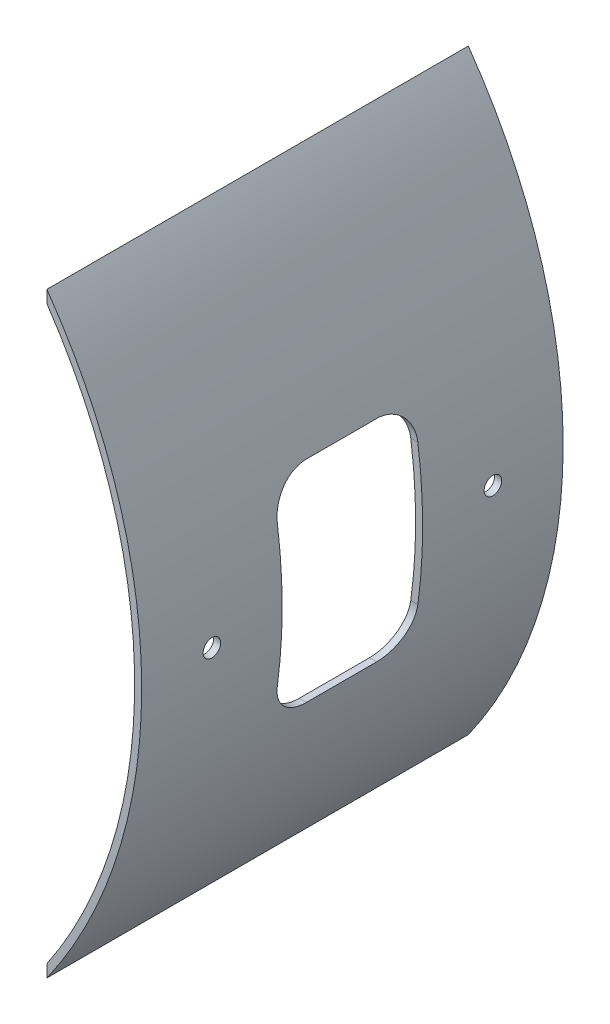
SolidWorks part; units mm, degrees
ref_plane "Face" through (0, 0, 0) normal (0, 0, 1) x (1, 0, 0)
ref_plane "Dessus" through (0, 0, 0) normal (0, 1, 0) x (1, 0, 0)
ref_plane "Droite" through (0, 0, 0) normal (1, 0, 0) x (0, 0, -1)
sketch "Esquisse1" plane through (0, 0, 0) normal (0, 0, 1) x (1, 0, 0)
  line L0 (120, 84.9058) -> (120, 81.3941)
  line L1 (120, -81.3941) -> (120, -84.9058)
  arc A0 (120, -84.9058) -> (120, 84.9058) centre (0, 0) ccw
  arc A1 (120, -81.3941) -> (120, 81.3941) centre (0, 0) ccw
  dimension "D1" = 294
  dimension "D2" = 2
  dimension "D3" = 120
extrude "Boss.-Extru.1" add sketch "Esquisse1" along normal blind 120
hole_wizard "Diamètre du perçage Ø5.0 (5)1" positions "Esquisse3D1" profile "Esquisse2" hole size "Ø5.0" standard "Din"
sketch3d "Esquisse3D1"
  point P0 (147, 0, 20)
  point P12 (147, 0, 100)
sketch "Esquisse2" plane through (147, 0, 20) normal (0, 1, 0) x (0, 0, -1)
  line L0 (0, 0) -> (0, 61.5022)
  line L1 (0, 61.5022) -> (2.5, 60)
  line L2 (2.5, 60) -> (2.5, 0)
  line L5 (2.5, 0) -> (0, 0)
  line L10 (0, 61.5022) -> (-2.5, 60) construction
  line L11 (0, -6.35) -> (0, 107.95) construction
  dimension "Diamètre du perçage" = 5
  dimension "Profondeur du perçage" = 60
  dimension "Angle de pointe" = 118
ref_axis "Axe1" through (0, 0, 120) along (0, 0, -1)
sketch "Esquisse3" plane through (0, 0, 0) normal (1, 0, 0) x (0, 0, -1)
  line L0 (0, -84.9058) -> (0, 84.9058) construction
  line L1 (-70, 30) -> (-50, 30)
  line L2 (-80, 20) -> (-80, -20)
  line L3 (-70, -30) -> (-50, -30)
  line L4 (-40, 20) -> (-40, -20)
  arc A0 (-50, -30) -> (-40, -20) centre (-50, -20) ccw
  arc A1 (-40, 20) -> (-50, 30) centre (-50, 20) ccw
  arc A2 (-70, -30) -> (-80, -20) centre (-70, -20) cw
  arc A3 (-80, 20) -> (-70, 30) centre (-70, 20) cw
  point P11 (-40, 30)
  point P16 (-80, 30)
  dimension "D5" = 10
  dimension "D1" = 40
  dimension "D2" = 40
  dimension "D3" = 30
  dimension "D4" = 30
extrude "Enlèv. mat.-Extru.2" cut sketch "Esquisse3" along normal through all
